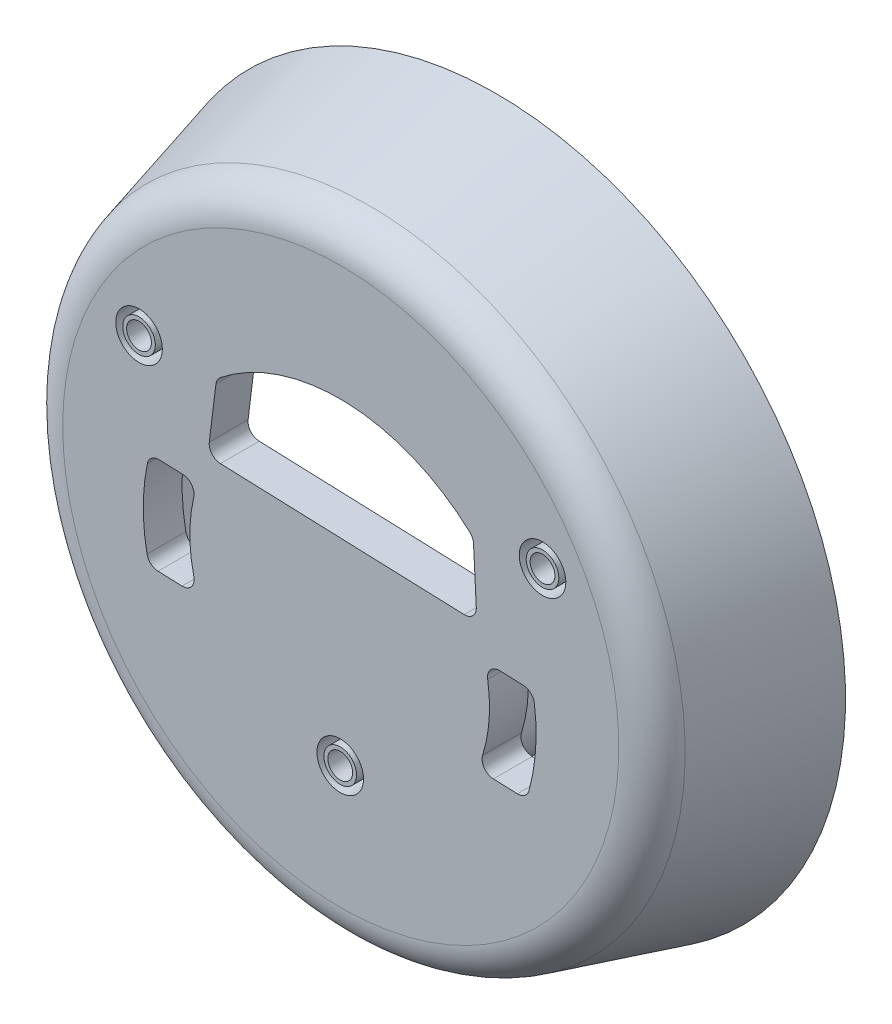
SolidWorks part; units mm, degrees
ref_plane "Alzado" through (0, 0, 0) normal (0, 0, 1) x (1, 0, 0)
ref_plane "Planta" through (0, 0, 0) normal (0, 1, 0) x (1, 0, 0)
ref_plane "Vista lateral" through (0, 0, 0) normal (1, 0, 0) x (0, 0, -1)
sketch "Croquis1" plane through (0, 0, 0) normal (0, 0, 1) x (1, 0, 0)
  line L0 (38.4373, 21.0977) -> (41.485, 20.9866) construction
  line L1 (40.7238, 8.506) -> (37.6297, 8.6189) construction
  line L2 (35.0786, 33.598) -> (35.4325, 26.6381) construction
  line L3 (1.0488, 27.8925) -> (1.9089, 34.8081) construction
  line L4 (33.8797, 25.063) -> (2.4827, 26.2084) construction
  line L5 (-2.3518, 22.5858) -> (-5.3995, 22.697) construction
  line L6 (-5.5496, 10.1941) -> (-2.4555, 10.0812) construction
  line L7 (38.4373, 21.0977) -> (41.485, 20.9866)
  line L8 (40.7238, 8.506) -> (37.6297, 8.6189)
  line L9 (35.0786, 33.598) -> (35.4325, 26.6381)
  line L10 (1.0488, 27.8925) -> (1.9089, 34.8081)
  line L11 (33.8797, 25.063) -> (2.4827, 26.2084)
  line L12 (-2.3518, 22.5858) -> (-5.3995, 22.697)
  line L13 (-5.5496, 10.1941) -> (-2.4555, 10.0812)
  arc A0 (38.4373, 21.0977) -> (36.9011, 19.3641) centre (38.3826, 19.5987) ccw construction
  arc A1 (42.9172, 19.6856) -> (41.485, 20.9866) centre (41.4303, 19.4876) ccw construction
  arc A2 (42.2242, 9.6053) -> (42.9172, 19.6856) centre (17.8423, 16.3454) ccw construction
  arc A3 (40.7238, 8.506) -> (42.2242, 9.6053) centre (40.7785, 10.005) ccw construction
  arc A4 (36.2532, 10.5671) -> (36.9011, 19.3641) centre (17.8423, 16.3454) ccw construction
  arc A5 (36.2532, 10.5671) -> (37.6297, 8.6189) centre (37.6844, 10.1179) ccw construction
  arc A6 (33.8797, 25.063) -> (35.4325, 26.6381) centre (33.9344, 26.562) ccw construction
  arc A7 (35.0786, 33.598) -> (34.5939, 34.6278) centre (33.5805, 33.5219) ccw construction
  arc A8 (34.5939, 34.6278) -> (2.4673, 35.7998) centre (17.8423, 16.3454) ccw construction
  arc A9 (2.4673, 35.7998) -> (1.9089, 34.8081) centre (3.3974, 34.623) ccw construction
  arc A10 (1.0488, 27.8925) -> (2.4827, 26.2084) centre (2.5373, 27.7074) ccw construction
  arc A11 (-0.946, 20.7448) -> (-2.3518, 22.5858) centre (-2.4065, 21.0868) ccw construction
  arc A12 (-5.3995, 22.697) -> (-6.9226, 21.5038) centre (-5.4541, 21.198) ccw construction
  arc A13 (-6.9226, 21.5038) -> (-6.966, 11.3999) centre (17.8423, 16.3454) ccw construction
  arc A14 (-6.966, 11.3999) -> (-5.5496, 10.1941) centre (-5.495, 11.6931) ccw construction
  arc A15 (-2.4555, 10.0812) -> (-0.9408, 11.924) centre (-2.4009, 11.5803) ccw construction
  arc A16 (-0.946, 20.7448) -> (-0.9408, 11.924) centre (17.8423, 16.3454) ccw construction
  arc A17 (38.4373, 21.0977) -> (36.9011, 19.3641) centre (38.3826, 19.5987) ccw
  arc A18 (42.9172, 19.6856) -> (41.485, 20.9866) centre (41.4303, 19.4876) ccw
  arc A19 (42.2242, 9.6053) -> (42.9172, 19.6856) centre (17.8423, 16.3454) ccw
  arc A20 (40.7238, 8.506) -> (42.2242, 9.6053) centre (40.7785, 10.005) ccw
  arc A21 (36.2532, 10.5671) -> (36.9011, 19.3641) centre (17.8423, 16.3454) ccw
  arc A22 (36.2532, 10.5671) -> (37.6297, 8.6189) centre (37.6844, 10.1179) ccw
  arc A23 (33.8797, 25.063) -> (35.4325, 26.6381) centre (33.9344, 26.562) ccw
  arc A24 (35.0786, 33.598) -> (34.5939, 34.6278) centre (33.5805, 33.5219) ccw
  arc A25 (34.5939, 34.6278) -> (2.4673, 35.7998) centre (17.8423, 16.3454) ccw
  arc A26 (2.4673, 35.7998) -> (1.9089, 34.8081) centre (3.3974, 34.623) ccw
  arc A27 (1.0488, 27.8925) -> (2.4827, 26.2084) centre (2.5373, 27.7074) ccw
  arc A28 (-0.946, 20.7448) -> (-2.3518, 22.5858) centre (-2.4065, 21.0868) ccw
  arc A29 (-5.3995, 22.697) -> (-6.9226, 21.5038) centre (-5.4541, 21.198) ccw
  arc A30 (-6.9226, 21.5038) -> (-6.966, 11.3999) centre (17.8423, 16.3454) ccw
  arc A31 (-6.966, 11.3999) -> (-5.5496, 10.1941) centre (-5.495, 11.6931) ccw
  arc A32 (-2.4555, 10.0812) -> (-0.9408, 11.924) centre (-2.4009, 11.5803) ccw
  arc A33 (-0.946, 20.7448) -> (-0.9408, 11.924) centre (17.8423, 16.3454) ccw
sketch "Croquis2" plane through (23.7696, 178.8214, 100) normal (0, 0, -1) x (-0.9993, 0.0365, 0)
  circle A0 centre (0, -158.6892) radius 45
  dimension "D1" = 90
extrude "Saliente-Extruir2" add sketch "Croquis2" against normal blind 20 draft 15
extrude "Cortar-Extruir2" cut sketch "Croquis1" along normal up to next
shell "Vaciado1" thickness 5 removed face at (39.9612, 21.0421, 110) removed face at (42.32, 20.467, 110) removed face at (42.8249, 14.628, 110) removed face at (41.5695, 8.9254, 110) removed face at (36.7004, 9.4226, 110) removed face at (39.1767, 8.5624, 110) removed face at (36.8319, 14.9468, 110) removed face at (37.4646, 20.4122, 110) removed face at (34.8294, 25.6797, 110) removed face at (35.2555, 30.1181, 110) removed face at (34.887, 34.1368, 110) removed face at (2.1393, 35.3315, 110) removed face at (1.5805, 26.8927, 110) removed face at (-1.4701, 10.8152, 110) removed face at (-4.0026, 10.1377, 110) removed face at (-6.3626, 10.674, 110) removed face at (-7.1991, 16.4529, 110) removed face at (-6.2701, 22.2396, 110) removed face at (-3.8756, 22.6414, 110) removed face at (-1.4316, 21.8312, 110) removed face at (-1.1988, 16.3342, 110) removed face at (18.1812, 25.6357, 110) removed face at (18.6384, 38.1696, 110) removed face at (1.4788, 31.3503, 110) removed face at (-4.0111, 16.3902, 100)
sketch "Croquis3" plane through (0, 0, 120) normal (0, 0, 1) x (1, 0, 0)
  line L0 (17.9133, 27.8535) -> (17.9133, 54.9833) construction
  line L1 (17.9843, 20.2376) -> (-16.3459, 0.4171) construction
  line L2 (17.9843, 20.2376) -> (-16.3459, 40.0582) construction
  circle A0 centre (17.9843, 20.2376) radius 39.641 construction
  circle A1 centre (43.965, 35.2376) radius 8
  circle A2 centre (-7.9965, 35.2376) radius 8
  circle A3 centre (17.9133, 0.2378) radius 8
  circle A4 centre (17.9843, 20.2376) radius 39.641 construction
  circle A5 centre (17.9843, 20.2376) radius 39.641 construction
  dimension "D3" = 16
  dimension "D4" = 16
  dimension "D5" = 16
  dimension "D1" = 60
  dimension "D2" = 60
  dimension "D6" = 30
  dimension "D7" = 30
  dimension "D8" = 20
extrude "Saliente-Extruir4" add sketch "Croquis3" against normal up to surface (20 mm away) up to face at (-21.8394, 20.2376, 100)
sketch "Croquis4" plane through (0, 0, 120) normal (0, 0, 1) x (1, 0, 0)
  circle A0 centre (43.965, 35.2376) radius 8 construction
  circle A1 centre (-7.9965, 35.2376) radius 8 construction
  circle A2 centre (17.9133, 0.2378) radius 8 construction
  circle A3 centre (43.965, 35.2376) radius 8 construction
  circle A4 centre (-7.9965, 35.2376) radius 8 construction
  circle A5 centre (17.9133, 0.2378) radius 8 construction
  circle A6 centre (-7.9965, 35.2376) radius 3
  circle A7 centre (43.965, 35.2376) radius 3
  circle A8 centre (17.9133, 0.2378) radius 3
  dimension "D1" = 6
  dimension "D2" = 6
  dimension "D3" = 6
extrude "Cortar-Extruir3" cut sketch "Croquis4" against normal offset from surface (15 mm away) 5 up to face at (35.965, 35.2376, 100)
sketch "Croquis5" plane through (0, 0, 120) normal (0, 0, 1) x (1, 0, 0)
  circle A0 centre (-7.9965, 35.2376) radius 1.6
  circle A1 centre (43.965, 35.2376) radius 1.6
  circle A2 centre (17.9133, 0.2378) radius 1.6
  dimension "D1" = 3.2
  dimension "D2" = 3.2
  dimension "D3" = 3.2
extrude "Cortar-Extruir4" cut sketch "Croquis5" against normal up to surface (20 mm away) up to face at (35.965, 35.2376, 100)
fillet "Redondeo1" radius 5 1 edges at (-21.6568, 20.2376, 120)
sketch "Croquis6" plane through (0, 0, 120) normal (0, 0, 1) x (1, 0, 0)
  circle A0 centre (-7.9965, 35.2376) radius 1.6 construction
  circle A1 centre (43.965, 35.2376) radius 1.6 construction
  circle A2 centre (17.9133, 0.2378) radius 1.6 construction
  circle A3 centre (-7.9965, 35.2376) radius 1.6
  circle A4 centre (43.965, 35.2376) radius 1.6
  circle A5 centre (17.9133, 0.2378) radius 1.6
extrude "Extruir-Lámina2" add sketch "Croquis6" against normal up to surface (15 mm away) thin up to face at (-9.5965, 35.2376, 105) thin type one direction wall 0.5
sketch "Croquis8" plane through (0, 0, 105) normal (0, 0, 1) x (1, 0, 0)
  circle A0 centre (-7.9965, 35.2376) radius 1.6 construction
  circle A1 centre (43.965, 35.2376) radius 1.6 construction
  circle A2 centre (17.9133, 0.2378) radius 1.6 construction
  circle A3 centre (-7.9965, 35.2376) radius 1.6
  circle A4 centre (43.965, 35.2376) radius 1.6
  circle A5 centre (17.9133, 0.2378) radius 1.6
extrude "Cortar-Extruir-Lámina2" cut sketch "Croquis8" along normal blind 0.2 thin thin type one direction wall 0.5
equation "\"D7@Croquis3\"=\"D6@Croquis3\""
equation "\"D5@Croquis3\"=\"D3@Croquis3\""
equation "\"D4@Croquis3\"=\"D3@Croquis3\""
